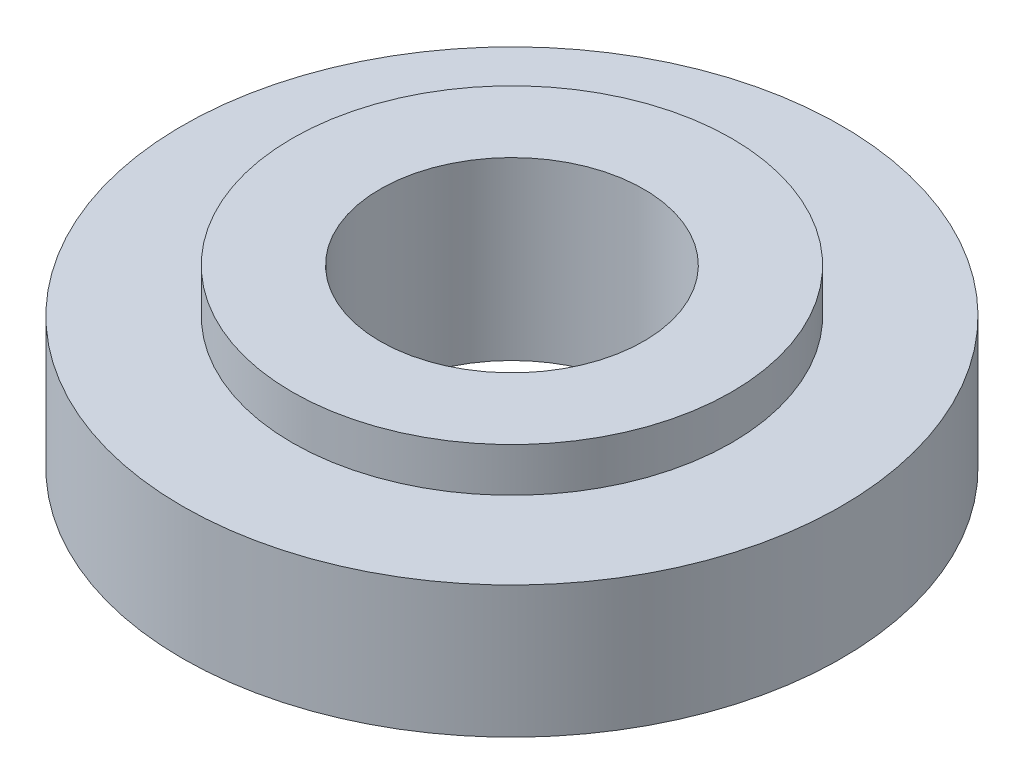
SolidWorks part; units mm, degrees
ref_plane "Front Plane" through (0, 0, 0) normal (0, 0, 1) x (1, 0, 0)
ref_plane "Top Plane" through (0, 0, 0) normal (0, 1, 0) x (1, 0, 0)
ref_plane "Right Plane" through (0, 0, 0) normal (1, 0, 0) x (0, 0, -1)
sketch "Sketch1" plane through (0, 0, 0) normal (0, 1, 0) x (1, 0, 0)
  circle A0 centre (0, 0) radius 3.75
  circle A1 centre (0, 0) radius 2.5
  circle A2 centre (0, 0) radius 1.5
  dimension "D1" = 3
  dimension "D2" = 5
  dimension "D3" = 7.5
extrude "Boss-Extrude1" add sketch "Sketch1" against normal blind 1.5 contours A0 A1 | A1 A2 region at (-3.6439, 0, 0) region at (-2.4293, 0, 0)
extrude "Boss-Extrude2" add sketch "Sketch1<4>" along normal blind 0.5 contours A1 A2 region at (-2.4293, 0, 0)
sketch "Sketch1<4>" plane through (0, 0, 0) normal (0, 1, 0) x (1, 0, 0) same geometry as "Sketch1"
